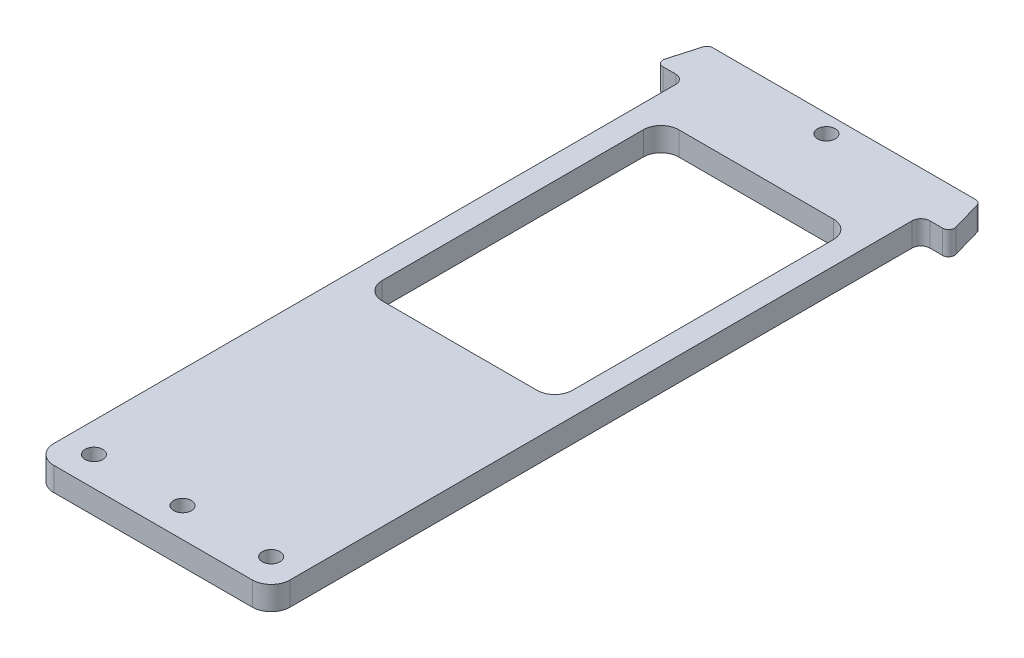
SolidWorks part; units mm, degrees
ref_plane "Front Plane" through (0, 0, 0) normal (0, 0, 1) x (1, 0, 0)
ref_plane "Top Plane" through (0, 0, 0) normal (0, 1, 0) x (1, 0, 0)
ref_plane "Right Plane" through (0, 0, 0) normal (1, 0, 0) x (0, 0, -1)
sketch "Sketch1" plane through (0, 0, 0) normal (0, 1, 0) x (1, 0, 0)
  line L0 (0, 0) -> (40, 0)
  line L1 (0, 117) -> (40, 117)
  line L2 (3.9, 102.1) -> (36.1, 102.1)
  line L3 (3.9, 102.1) -> (3.9, 51.9)
  line L4 (3.9, 51.9) -> (36.1, 51.9)
  line L5 (36.1, 102.1) -> (36.1, 51.9)
  line L6 (40, 117) -> (40, 0)
  line L7 (0, 117) -> (0, 0)
  line L8 (20, 5) -> (20, 0) construction
  circle A0 centre (5, 5) radius 1.5
  circle A1 centre (35, 5) radius 1.5
  circle A2 centre (20, 5) radius 1.5
  circle A3 centre (20, 114) radius 1.5
  dimension "D5" = 3
  dimension "D7" = 3
  dimension "D1" = 32.2
  dimension "D2" = 50.2
  dimension "D3" = 14.9
  dimension "D4" = 51.9
  dimension "D6" = 5
  dimension "D8" = 3
  dimension "D9" = 3.9
  dimension "D10" = 3.9
  dimension "D11" = 20
  dimension "D12" = 5
  dimension "D13" = 5
extrude "Boss-Extrude1" add sketch "Sketch1" along normal blind 4
fillet "Fillet1" radius 3 4 edges at (3.9, 2, -102.1) (36.1, 2, -51.9) (3.9, 2, -51.9) (36.1, 2, -102.1)
sketch "Sketch2" plane through (0, 4, 0) normal (0, 1, 0) x (1, 0, 0)
  line L0 (0, 117) -> (-3, 117)
  line L1 (-3, 117) -> (-5, 110)
  line L2 (-5, 110) -> (0, 110)
  line L3 (0, 117) -> (0, 0) construction
  line L4 (0, 110) -> (0, 117)
  line L5 (40, 117) -> (43, 117)
  line L6 (43, 117) -> (45, 110)
  line L7 (45, 110) -> (40, 110)
  line L8 (40, 0) -> (40, 117) construction
  line L9 (40, 110) -> (40, 117)
  dimension "D1" = 7
  dimension "D2" = 5
  dimension "D3" = 3
extrude "Boss-Extrude2" add sketch "Sketch2" against normal up to surface (4 mm away) up to face at (20, 0, -3.5)
fillet "Fillet2" radius 1 4 edges at (45, 2, -110) (43, 2, -117) (-5, 2, -110) (-3, 2, -117)
fillet "Fillet3" radius 1.5 2 edges
fillet "Fillet4" radius 3.2 2 edges at (0, 2, 0) (40, 2, 0)
